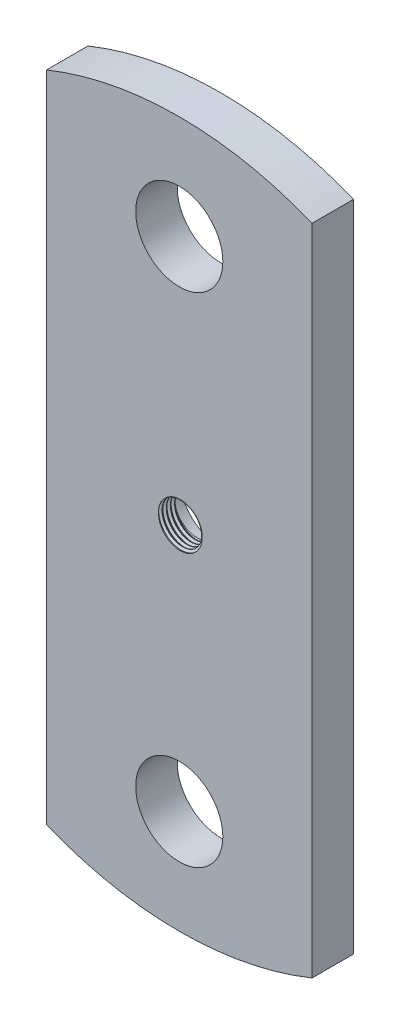
SolidWorks part; units mm, degrees
material "Alloy Steel"
ref_plane "Front Plane" through (0, 0, 0) normal (0, 0, 1) x (1, 0, 0)
ref_plane "Top Plane" through (0, 0, 0) normal (0, 1, 0) x (1, 0, 0)
ref_plane "Right Plane" through (0, 0, 0) normal (1, 0, 0) x (0, 0, -1)
sketch "Sketch1" plane through (0, 0, 0) normal (0, 0, 1) x (1, 0, 0)
  line L0 (0, 0) -> (-14703.0923, 0) construction
  line L1 (0, 0) -> (0, -14703.0923) construction
  line L2 (32, 78.7464) -> (32, -78.7464)
  line L3 (-32, 78.7464) -> (-32, -78.7464)
  circle A0 centre (0, 0) radius 5
  circle A1 centre (0, 0) radius 10
  circle A2 centre (0, 60) radius 10.5
  circle A3 centre (0, -60) radius 10.5
  arc A4 (32, 78.7464) -> (-32, 78.7464) centre (0, 0) ccw
  arc A5 (-32, -78.7464) -> (32, -78.7464) centre (0, 0) ccw
  point P16 (32, 0)
  dimension "D1" = 10
  dimension "D2" = 20
  dimension "D3" = 21
  dimension "D5" = 170
  dimension "D4" = 120
  dimension "D6" = 64
extrude "Boss-Extrude1" add sketch "Sketch1" along normal blind 10 contours L3 A5 L2 A4 A3 A2 A1 | A1 A0 region at (30.1835, 0, 0) region at (-9.7172, 0, 0)
extrude "Cut-Extrude2" cut sketch "Sketch1<7>" along normal blind 5.5 contours A1 A0 region at (-9.7172, 0, 0)
sketch "Sketch1<7>" plane through (0, 0, 0) normal (0, 0, 1) x (1, 0, 0) same geometry as "Sketch1"
thread "Thread1" pitch 1 method cut profile "Thread Profile1" start angle 0, offset 10, length 30, pitch 1, diameter 10
ref_plane "Plane1" through (-5, 0, 20) normal (0, 1, 0) x (1, 0, 0)
sketch "Thread Profile1" plane through (-5, 0, 20) normal (0, 1, 0) x (1, 0, 0)
  line L0 (0, 0) -> (0, 1) construction
  line L11 (0, 0) -> (0, 0.875)
  line L12 (0, 0.875) -> (-0.5413, 0.5625)
  line L13 (-0.5413, 0.5625) -> (-0.5413, 0.3125)
  line L15 (-0.5413, 0.3125) -> (0, 0)
  line L17 (-0.5413, 0.4375) -> (0, 0.4375) construction
  point P2 (0, 0)
  dimension "Pitch" = 1
  dimension "Profile_Angle" = 60
  dimension "Profile_Land" = 0.25
  dimension "Profile_Height" = 0.5413
